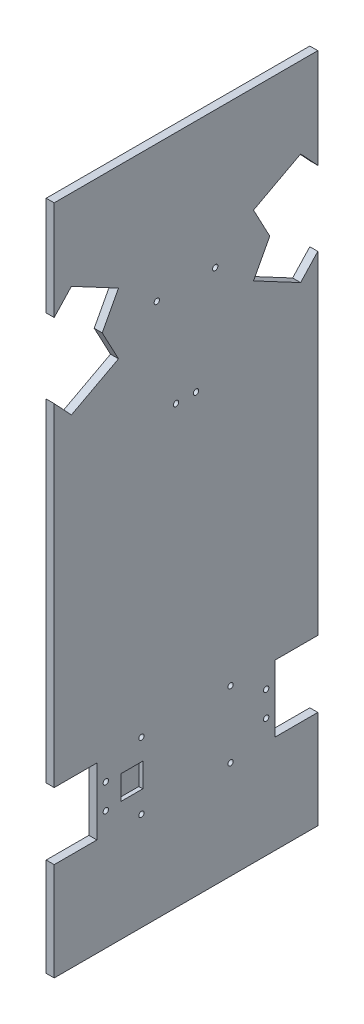
SolidWorks part; units mm, degrees
ref_plane "前视基准面" through (0, 0, 0) normal (0, 0, 1) x (1, 0, 0)
ref_plane "上视基准面" through (0, 0, 0) normal (0, 1, 0) x (1, 0, 0)
ref_plane "右视基准面" through (0, 0, 0) normal (1, 0, 0) x (0, 0, -1)
other "Configuration Table"
sketch "草图1" plane through (0, 0, 0) normal (1, 0, 0) x (0, 0, -1)
  line L1 (0, 0) -> (98.8, 0)
  line L2 (0, 0) -> (0, -251.6)
  line L3 (0, -251.6) -> (98.8, -251.6)
  line L4 (98.8, 0) -> (98.8, -251.6)
  dimension "D1" = 251.6
  dimension "D2" = 98.8
extrude "凸台-拉伸1" add sketch "草图1" along normal blind 3
sketch "草图2" plane through (3, 0, 0) normal (1, 0, 0) x (0, 0, -1)
  line L0 (0, -51.2) -> (98.8, -51.2) construction
  line L1 (0, 0) -> (0, -251.6) construction
  line L2 (98.8, -251.6) -> (98.8, 0) construction
  line L3 (98.8, 0) -> (0, 0) construction
  line L4 (0, -202.3) -> (98.8, -202.3) construction
  line L6 (0, -38.7) -> (16, -38.7)
  line L7 (0, -38.7) -> (0, -63.7)
  line L8 (0, -63.7) -> (16, -63.7)
  line L9 (16, -38.7) -> (16, -63.7)
  line L10 (98.8, -38.7) -> (82.8, -38.7)
  line L11 (98.8, -38.7) -> (98.8, -63.7)
  line L12 (98.8, -63.7) -> (82.8, -63.7)
  line L13 (82.8, -38.7) -> (82.8, -63.7)
  line L14 (0, -189.8) -> (16, -189.8)
  line L15 (0, -189.8) -> (0, -214.8)
  line L16 (0, -214.8) -> (16, -214.8)
  line L17 (16, -189.8) -> (16, -214.8)
  line L18 (82.8, -189.8) -> (98.8, -189.8)
  line L19 (82.8, -189.8) -> (82.8, -214.8)
  line L20 (82.8, -214.8) -> (98.8, -214.8)
  line L21 (98.8, -189.8) -> (98.8, -214.8)
  dimension "D1" = 51.2
  dimension "D2" = 151.1
  dimension "D3" = 25
  dimension "D4" = 16
  dimension "D5" = 25
  dimension "D6" = 16
extrude "切除-拉伸1" cut sketch "草图2" against normal through all
sketch "草图3" plane through (3, 0, 0) normal (1, 0, 0) x (0, 0, -1)
  line L0 (49.4, 0) -> (49.4, -251.6) construction
  line L1 (98.8, 0) -> (0, 0) construction
  line L2 (0, -251.6) -> (98.8, -251.6) construction
sketch "草图4" plane through (3, 0, 0) normal (1, 0, 0) x (0, 0, -1)
  line L0 (16, -51.2) -> (82.8, -51.2) construction
  line L1 (16, -63.7) -> (16, -38.7) construction
  line L2 (82.8, -38.7) -> (82.8, -63.7) construction
  line L3 (18, -51.2) -> (24.1031, -39.7217)
  line L4 (24.1031, -39.7217) -> (6.4442, -30.3323)
  line L5 (6.4442, -30.3323) -> (0, -37.2428)
  line L6 (0, 0) -> (0, -38.7) construction
  line L7 (18, -51.2) -> (24.1031, -62.6783)
  line L8 (24.1031, -62.6783) -> (6.4442, -72.0677)
  line L9 (6.4442, -72.0677) -> (0, -65.1572)
  line L10 (0, -63.7) -> (0, -189.8) construction
  line L11 (80.8, -51.2) -> (74.6969, -62.6783)
  line L12 (74.6969, -62.6783) -> (92.3558, -72.0677)
  line L13 (92.3558, -72.0677) -> (98.8, -65.1572)
  line L14 (98.8, -189.8) -> (98.8, -63.7) construction
  line L15 (80.8, -51.2) -> (74.6969, -39.7217)
  line L16 (74.6969, -39.7217) -> (92.3558, -30.3323)
  line L17 (92.3558, -30.3323) -> (98.8, -37.2428)
  line L18 (98.8, -38.7) -> (98.8, 0) construction
  line L19 (16, -51.2) -> (18, -51.2) construction
  line L20 (80.8, -51.2) -> (82.8, -51.2) construction
  line M10 (98.8, -63.7) -> (82.8, -63.7)
  line M11 (82.8, -63.7) -> (82.8, -38.7)
  line M12 (82.8, -38.7) -> (98.8, -38.7)
  line M13 (98.8, -38.7) -> (98.8, 0)
  line M15 (0, 0) -> (0, -38.7)
  line M16 (0, -38.7) -> (16, -38.7)
  line M17 (16, -38.7) -> (16, -63.7)
  line M18 (16, -63.7) -> (0, -63.7)
  line M19 (0, -63.7) -> (0, -189.8)
  line M29 (98.8, -189.8) -> (98.8, -63.7)
  dimension "D1" = 2
  dimension "D2" = 62
  dimension "D3" = 20
  dimension "D4" = 13
  dimension "D5" = 62
  dimension "D6" = 105
  dimension "D7" = 105
  dimension "D8" = 105
  dimension "D9" = 105
extrude "切除-拉伸2" cut sketch "草图4" against normal through all contours L9 L8 L7 L3 L4 L5 M15 M16 M17 M18 M19 | L17 L16 L15 L11 L12 L13 M29 M10 M11 M12 M13 region at (3, -57.1654, -20.626) region at (3, -45.2346, -78.174)
sketch "草图5" plane through (0, 0, 0) normal (-1, 0, 0) x (0, 0, 1)
  circle A0 centre (-38.45, -51.2) radius 1.5
  circle A1 centre (-38.45, -51.2) radius 1
  circle A2 centre (-60.35, -51.2) radius 1.5
  circle A3 centre (-60.35, -51.2) radius 1
  dimension "D1" = 2
  dimension "D2" = 3
extrude "切除-拉伸3" cut sketch "草图5" against normal through all contours A1 | A3
extrude "切除-拉伸4" cut sketch "草图5<3>" against normal blind 1.5
sketch "草图5<3>" plane through (0, 0, 0) normal (-1, 0, 0) x (0, 0, 1) same geometry as "草图5"
sketch "草图6" plane through (0, 0, 0) normal (-1, 0, 0) x (0, 0, 1)
  line L0 (-98.8, 0) -> (0, 0) construction
  line L1 (-45.65, -88) -> (-53.15, -88) construction
  line L2 (-49.4, -88) -> (-49.4, 0) construction
  circle A0 centre (-45.65, -88) radius 1
  circle A1 centre (-45.65, -88) radius 1.5
  circle A2 centre (-53.15, -88) radius 1
  circle A3 centre (-53.15, -88) radius 1.5
  dimension "D1" = 2
  dimension "D2" = 3
  dimension "D3" = 88
  dimension "D4" = 7.5
extrude "切除-拉伸7" cut sketch "草图6" against normal blind 1.5
extrude "切除-拉伸8" cut sketch "草图6<2>" against normal through all contours A0 | A2
sketch "草图6<2>" plane through (0, 0, 0) normal (-1, 0, 0) x (0, 0, 1) same geometry as "草图6"
sketch "草图7" plane through (3, 0, 0) normal (1, 0, 0) x (0, 0, -1)
  line L1 (25, -197.8) -> (33.2, -197.8)
  line L2 (25, -197.8) -> (25, -206.8)
  line L3 (25, -206.8) -> (33.2, -206.8)
  line L4 (33.2, -197.8) -> (33.2, -206.8)
  line L5 (0, -65.1572) -> (0, -189.8) construction
  line L6 (16, -202.3) -> (25, -202.3) construction
  line L7 (16, -214.8) -> (16, -189.8) construction
  dimension "D1" = 25
  dimension "D2" = 8.2
  dimension "D3" = 9
extrude "切除-拉伸9" cut sketch "草图7" against normal blind 1.5
sketch "草图8" plane through (0, 0, 0) normal (-1, 0, 0) x (0, 0, 1)
  circle A0 centre (-79.45, -197.6) radius 1.5
  circle A1 centre (-79.45, -197.6) radius 1
  circle A2 centre (-79.45, -207) radius 1.5
  circle A3 centre (-79.45, -207) radius 1
  circle A6 centre (-19.35, -207) radius 1.5
  circle A7 centre (-19.35, -207) radius 1
  circle A8 centre (-19.35, -197.6) radius 1.5
  circle A9 centre (-19.35, -197.6) radius 1
  dimension "D1" = 2
  dimension "D2" = 3
extrude "切除-拉伸10" cut sketch "草图8" against normal through all contours A7 | A9 | A3 | A1
extrude "切除-拉伸11" cut sketch "草图8<3>" against normal blind 1.5
sketch "草图8<3>" plane through (0, 0, 0) normal (-1, 0, 0) x (0, 0, 1) same geometry as "草图8"
sketch "草图9" plane through (0, 0, 0) normal (-1, 0, 0) x (0, 0, 1)
  line L0 (-82.8, -189.8) -> (-66.1, -189.8) construction
  line L1 (-82.8, -189.8) -> (-82.8, -214.8) construction
  line L2 (-98.8, -189.8) -> (-82.8, -189.8) construction
  line L3 (-66.1, -189.8) -> (-49.4, -189.8) construction
  line L4 (-49.4, -189.8) -> (-32.7, -189.8) construction
  line L5 (-32.7, -189.8) -> (-16, -189.8) construction
  line L6 (-82.8, -214.8) -> (-66.1, -214.8) construction
  line L7 (-66.1, -214.8) -> (-49.4, -214.8) construction
  line L8 (-49.4, -214.8) -> (-32.7, -214.8) construction
  line L9 (-32.7, -214.8) -> (-16, -214.8) construction
  line L10 (0, -214.8) -> (-16, -214.8) construction
  line L11 (-16, -189.8) -> (0, -189.8) construction
  circle A0 centre (-66.1, -189.8) radius 1.5
  circle A1 centre (-66.1, -189.8) radius 1
  circle A2 centre (-32.7, -189.8) radius 1.5
  circle A3 centre (-32.7, -189.8) radius 1
  circle A4 centre (-66.1, -214.8) radius 1.5
  circle A5 centre (-66.1, -214.8) radius 1
  circle A6 centre (-32.7, -214.8) radius 1.5
  circle A7 centre (-32.7, -214.8) radius 1
  dimension "D1" = 2
  dimension "D2" = 3
extrude "切除-拉伸12" cut sketch "草图9" against normal through all contours A1 | A3 | A7 | A5
extrude "切除-拉伸13" cut sketch "草图9<3>" against normal blind 1.5
sketch "草图9<3>" plane through (0, 0, 0) normal (-1, 0, 0) x (0, 0, 1) same geometry as "草图9"
